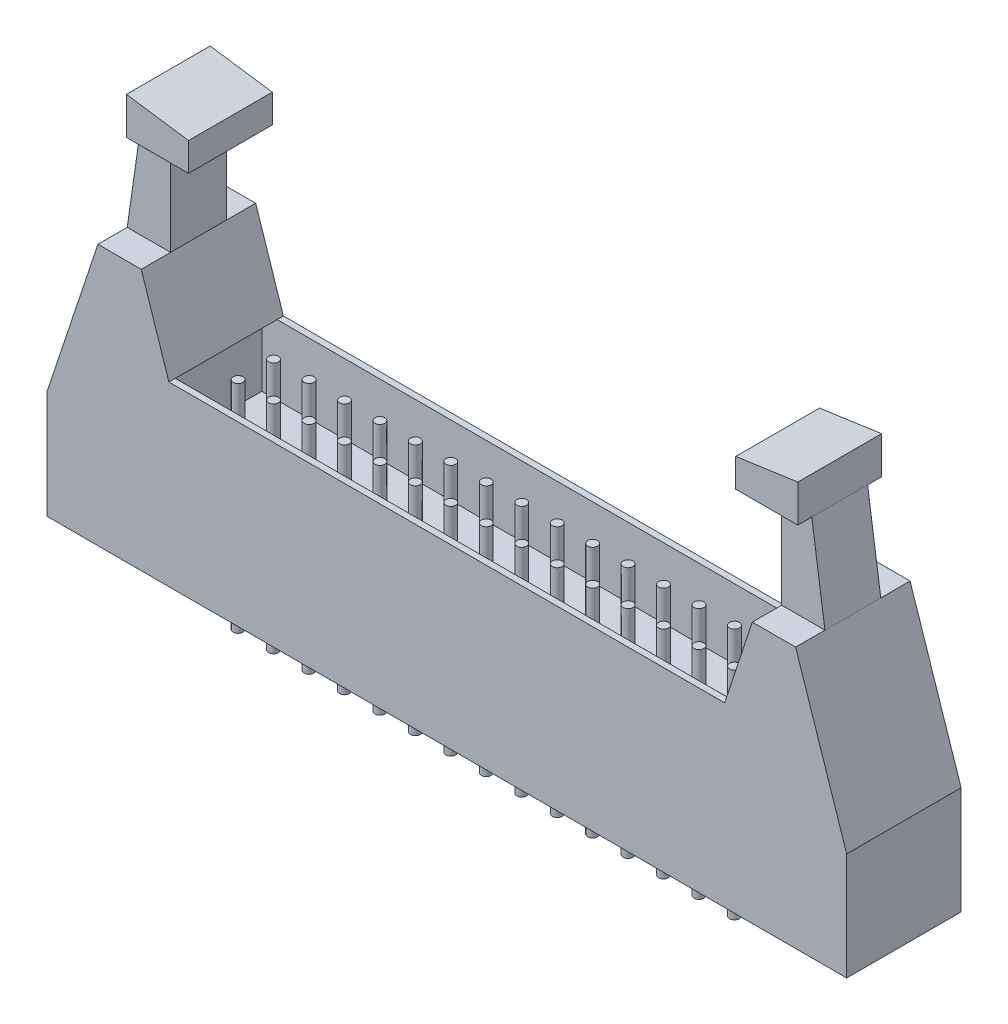
SolidWorks part; units mm, degrees
ref_plane "Спереди" through (0, 0, 0) normal (0, 0, 1) x (1, 0, 0)
ref_plane "Сверху" through (0, 0, 0) normal (0, 1, 0) x (1, 0, 0)
ref_plane "Справа" through (0, 0, 0) normal (1, 0, 0) x (0, 0, -1)
sketch "Эскиз2" plane through (0, 0, 0) normal (0, 0, 1) x (1, 0, 0)
  line L1 (21.8896, 14.8525) -> (19.9071, 8.85)
  line L2 (-28.65, 3.85) -> (-28.65, -3.85)
  line L3 (-28.65, -3.85) -> (28.65, -3.85)
  line L4 (-28.65, 3.85) -> (-24.9926, 14.8525)
  line L5 (-24.9926, 14.8525) -> (-21.8896, 14.8525)
  line L6 (-21.8896, 14.8525) -> (-19.9071, 8.85)
  line L7 (-19.9071, 8.85) -> (19.9071, 8.85)
  line L8 (24.9926, 14.8525) -> (21.8896, 14.8525)
  line L9 (28.65, 3.85) -> (24.9926, 14.8525)
  line L10 (28.65, 3.85) -> (28.65, -3.85)
  point P0 (0, 0)
  point P6 (0, 0)
extrude "Бобышка-Вытянуть1" add sketch "Эскиз2" along normal blind 4.1 and the other way blind 4.1
sketch "Эскиз3" plane through (0, 8.85, 0) normal (0, 1, 0) x (1, 0, 0)
  line L1 (-21, 3.6471) -> (21, 3.6471)
  line L2 (-21, 3.6471) -> (-21, -3.6471)
  line L3 (-21, -3.6471) -> (21, -3.6471)
  line L4 (21, 3.6471) -> (21, -3.6471)
  line L5 (-21, 3.6471) -> (21, -3.6471) construction
  line L6 (-21, -3.6471) -> (21, 3.6471) construction
  point P0 (0, 0)
extrude "Вырез-Вытянуть1" cut sketch "Эскиз3" against normal blind 5
ref_plane "Плоскость1" through (0, 0, 0) normal (0, 0, 1) x (1, 0, 0)
sketch "Эскиз4" plane through (0, 0, 0) normal (0, 0, 1) x (1, 0, 0)
  line L0 (-24.9926, 14.8525) -> (-21.8896, 14.8525)
  line L1 (-21.8896, 14.8525) -> (-21.8896, 21.4005)
  line L2 (-21.8896, 21.4005) -> (-24.0524, 21.4005)
  line L3 (-24.0524, 21.4005) -> (-24.9926, 14.8525)
  line L4 (0, 0) -> (0, 17.3404) construction
  line L5 (24.0524, 21.4005) -> (24.9926, 14.8525)
  line L6 (21.8896, 21.4005) -> (24.0524, 21.4005)
  line L7 (21.8896, 14.8525) -> (21.8896, 21.4005)
  line L8 (24.9926, 14.8525) -> (21.8896, 14.8525)
extrude "Бобышка-Вытянуть2" add sketch "Эскиз4" along normal blind 2 and the other way blind 2
sketch "Эскиз5" plane through (0, 0, 0) normal (0, 0, 1) x (1, 0, 0)
  line L0 (-24.0524, 21.4005) -> (-24.0524, 24.0749)
  line L1 (-24.0524, 24.0749) -> (-19.602, 23.4359)
  line L2 (-19.602, 23.4359) -> (-19.602, 21.4005)
  line L3 (-19.602, 21.4005) -> (-21.8896, 21.4005)
  line L4 (0, 0) -> (0, 17.0741) construction
  line L5 (19.602, 21.4005) -> (21.8896, 21.4005)
  line L6 (19.602, 23.4359) -> (19.602, 21.4005)
  line L7 (24.0524, 24.0749) -> (19.602, 23.4359)
  line L8 (24.0524, 21.4005) -> (24.0524, 24.0749)
  line L9 (-24.0524, 21.4005) -> (-21.8896, 21.4005)
  line L10 (24.0524, 21.4005) -> (21.8896, 21.4005)
extrude "Бобышка-Вытянуть3" add sketch "Эскиз5" along normal blind 3 and the other way blind 3
sketch "Эскиз6" plane through (0, -3.85, 0) normal (0, -1, 0) x (1, 0, 0)
  line L0 (0, 0) -> (-26.0337, 0) construction
  line L1 (0, 0) -> (25.4468, 0) construction
  line L2 (0, 0) -> (0, -1.27) construction
  line L3 (0, 0) -> (0, 1.27) construction
  circle A0 centre (0, 1.27) radius 0.35
  circle A1 centre (0, -1.27) radius 0.35
  circle A2 centre (2.54, -1.27) radius 0.35
  circle A3 centre (2.54, 1.27) radius 0.35
  circle A4 centre (5.08, -1.27) radius 0.35
  circle A5 centre (5.08, 1.27) radius 0.35
  circle A6 centre (7.62, -1.27) radius 0.35
  circle A7 centre (7.62, 1.27) radius 0.35
  circle A8 centre (10.16, -1.27) radius 0.35
  circle A9 centre (10.16, 1.27) radius 0.35
  circle A10 centre (12.7, -1.27) radius 0.35
  circle A11 centre (12.7, 1.27) radius 0.35
  circle A12 centre (15.24, -1.27) radius 0.35
  circle A13 centre (15.24, 1.27) radius 0.35
  circle A14 centre (17.78, -1.27) radius 0.35
  circle A15 centre (17.78, 1.27) radius 0.35
  circle A16 centre (-2.54, -1.27) radius 0.35
  circle A17 centre (-2.54, 1.27) radius 0.35
  circle A18 centre (-5.08, -1.27) radius 0.35
  circle A19 centre (-5.08, 1.27) radius 0.35
  circle A20 centre (-7.62, -1.27) radius 0.35
  circle A21 centre (-7.62, 1.27) radius 0.35
  circle A22 centre (-10.16, -1.27) radius 0.35
  circle A23 centre (-10.16, 1.27) radius 0.35
  circle A24 centre (-12.7, -1.27) radius 0.35
  circle A25 centre (-12.7, 1.27) radius 0.35
  circle A26 centre (-15.24, -1.27) radius 0.35
  circle A27 centre (-15.24, 1.27) radius 0.35
  circle A28 centre (-17.78, -1.27) radius 0.35
  circle A29 centre (-17.78, 1.27) radius 0.35
  dimension "D1" = 8
  dimension "D2" = 8
extrude "Бобышка-Вытянуть4" add sketch "Эскиз6" along normal blind 3 and the other way blind 12.5
